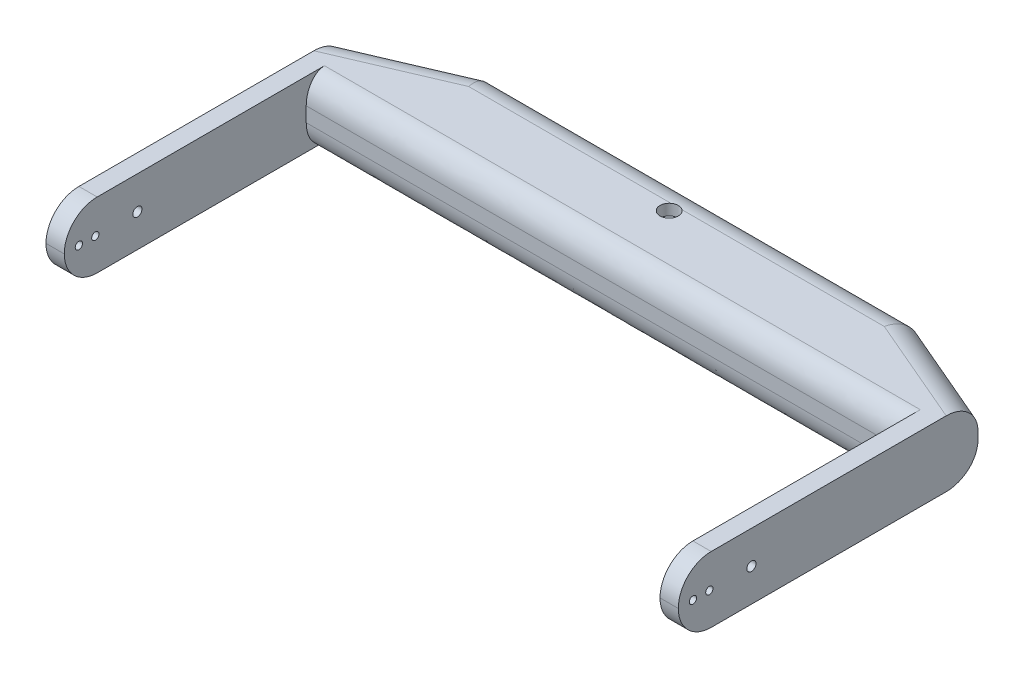
SolidWorks part; units mm, degrees
ref_plane "Front Plane" through (0, 0, 0) normal (0, 0, 1) x (1, 0, 0)
ref_plane "Top Plane" through (0, 0, 0) normal (0, 1, 0) x (1, 0, 0)
ref_plane "Right Plane" through (0, 0, 0) normal (1, 0, 0) x (0, 0, -1)
sketch "Sketch1" plane through (0, 0, 0) normal (1, 0, 0) x (0, 0, -1)
  line L0 (0, 0) -> (0, -37) construction
  line L1 (0, -37) -> (55, -37) construction
  line L2 (55, -37) -> (0, 0) construction
  line L3 (55, -37) -> (0, 24.0837) construction
  line L4 (0, 24.0837) -> (0, 0) construction
  line L5 (0, -37) -> (-55, -37) construction
  line L6 (-55, -37) -> (0, 0) construction
  line L7 (-55, -37) -> (0, 24.0837) construction
  dimension "D1" = 37
  dimension "D2" = 55
  dimension "D3" = 48
ref_plane "Plane1" through (0, 0, 0) normal (0, 1, 0) x (1, 0, 0)
sketch "Sketch2" plane through (0, 0, 0) normal (0, 1, 0) x (1, 0, 0)
  line L0 (-81.5, 0) -> (81.5, 0)
  line L1 (0, 17.8) -> (0, 0) construction
  line L2 (0, 0) -> (0, 55) construction
  line L3 (-40, 17.8) -> (40, 17.8) construction
  line L4 (-86.5, -5) -> (86.5, -5)
  line L5 (86.5, -5) -> (86.5, 22.8)
  line L6 (86.5, 22.8) -> (-86.5, 22.8)
  line L7 (-86.5, 22.8) -> (-86.5, -5)
  spline S0 degree 3 poles (-81.5, 0) (-74.4361, 13.8819) (-43.2594, 16.3622) (0, 18.5559) (43.2594, 16.3622) (74.4361, 13.8819) (81.5, 0) knots 0 0 0 0 0.237126 0.5 0.762874 1 1 1 1
  point P2 (0, 0)
  point P12 (0, 17.8)
  dimension "D1" = 163
  dimension "D2" = 80
  dimension "D3" = 17.8
  dimension "D4" = 10
  dimension "D5" = 10.5
  dimension "D6" = 36
  dimension "D7" = 16
  dimension "D8" = 10
  dimension "D9" = 36
  dimension "D10" = 5
  dimension "D11" = 5
  dimension "D12" = 5
  dimension "D13" = 5
extrude "Boss-Extrude1" add sketch "Sketch2" along normal blind 14
sketch "Sketch4" plane through (0, 14, 0) normal (0, 1, 0) x (1, 0, 0)
  line L0 (-86.5, 22.8) -> (86.5, 22.8)
  line L1 (86.5, 22.8) -> (86.5, -5)
  line L2 (86.5, -5) -> (-86.5, -5)
  line L3 (-86.5, -5) -> (-86.5, 22.8)
  line L4 (0, 0) -> (0, 55) construction
  line L5 (0, 13.8) -> (0, 17.8) construction
  circle A0 centre (0, 12.8) radius 1
  spline S0 degree 3 poles (81.5, 0) (74.4361, 13.8819) (43.2594, 16.3622) (0, 18.5559) (-43.2594, 16.3622) (-74.4361, 13.8819) (-81.5, 0) knots 0 0 0 0 0.237126 0.5 0.762874 1 1 1 1 construction
  dimension "D1" = 2
  dimension "D2" = 4
extrude "Boss-Extrude3" add sketch "Sketch4" along normal blind 4
sketch "Sketch5" plane through (0, 14, 0) normal (0, -1, 0) x (1, 0, 0)
  line L0 (0, -9.8) -> (-7.9313, -17.7313)
  line L1 (0, -55) -> (0, 0) construction
  line L2 (-7.9313, -17.7313) -> (-7.9313, -22.8)
  line L3 (86.5, -22.8) -> (-86.5, -22.8) construction
  line L4 (-7.9313, -22.8) -> (7.9313, -22.8)
  line L5 (7.9313, -22.8) -> (7.9313, -17.7313)
  line L6 (7.9313, -17.7313) -> (0, -9.8)
  line L7 (0, -17.8) -> (0, -22.8) construction
  line L8 (0.7071, -13.5071) -> (-1.5, -11.3) construction
  line L9 (0, -13.8) -> (0, -11.8) construction
  circle A1 centre (0, -12.8) radius 1 construction
  circle A2 centre (0, -12.8) radius 1
  spline S0 degree 3 poles (81.5, 0) (74.4361, -13.8819) (43.2594, -16.3622) (0, -18.5559) (-43.2594, -16.3622) (-74.4361, -13.8819) (-81.5, 0) knots 0 0 0 0 0.237126 0.5 0.762874 1 1 1 1 construction
  point P17 (0, -12.8)
  dimension "D1" = 8
  dimension "D2" = 45
extrude "Boss-Extrude4" add sketch "Sketch5" along normal blind 5.5
sketch "Sketch8" plane through (86.5, 0, 0) normal (1, 0, 0) x (0, 0, -1)
  line L0 (22.8, 0) -> (-71.2, 0)
  line L1 (-71.2, 0) -> (-71.2, 18)
  line L2 (-71.2, 18) -> (22.8, 18)
  line L3 (22.8, 18) -> (22.8, 0)
  line L4 (22.8, 9) -> (-71.2, 9) construction
  circle A0 centre (-51.2, 9) radius 1.25
  circle A1 centre (-62.7, 9) radius 1
  circle A2 centre (-67.2, 9) radius 1
  dimension "D1" = 74
  dimension "D2" = 2.5
  dimension "D3" = 20
  dimension "D4" = 11.5
  dimension "D5" = 2
  dimension "D6" = 4.5
extrude "Boss-Extrude6" add sketch "Sketch8" against normal up to vertex (5 mm away) up to point (81.5, 0, 0)
fillet "Fillet1" radius 9 2 edges at (84, 18, 71.2) (84, 0, 71.2)
mirror "Mirror1" about plane through (0, 0, 0) normal (1, 0, 0) of "Fillet1", "Boss-Extrude6"
fillet "Fillet2" radius 5 2 edges at (0, 0, 5) (0, 18, 5) second distance 7 first distance on face at (40.75, 0, 0) first distance on face at (0, 18, 26.65)
sketch "Sketch9" plane through (0, 18, 0) normal (0, 1, 0) x (1, 0, 0)
  circle A0 centre (0, 12.8) radius 2.5
  dimension "D1" = 5
extrude "Cut-Extrude1" cut sketch "Sketch9" against normal blind 3
sketch "Sketch14" plane through (0, 0, 0) normal (0, 1, 0) x (1, 0, 0)
  line L0 (86.5, 22.8) -> (86.5, 10.8)
  line L1 (86.5, -62.2) -> (86.5, 22.8) construction
  line L2 (86.5, 10.8) -> (58.5, 22.8)
  line L4 (58.5, 22.8) -> (86.5, 22.8)
  line L5 (0, -9.933) -> (0, 9.933) construction
  line L6 (-86.5, 22.8) -> (-86.5, 10.8)
  line L7 (-58.5, 22.8) -> (-86.5, 22.8)
  line L8 (-86.5, 10.8) -> (-58.5, 22.8)
  point P7 (86.5, 22.8)
  point P13 (0, 0)
  point P15 (69.4717, 22.8)
  dimension "28" = 28
  dimension "D2" = 12
extrude "Cut-Extrude2" cut sketch "Sketch14" against normal through all both and the other way through all
fillet "Fillet5" radius 8 6 edges at (72.5, 0, -16.8) (0, 0, -22.8) (-72.5, 0, -16.8) (0, 18, -22.8) (-72.5, 18, -16.8) (72.5, 18, -16.8)
